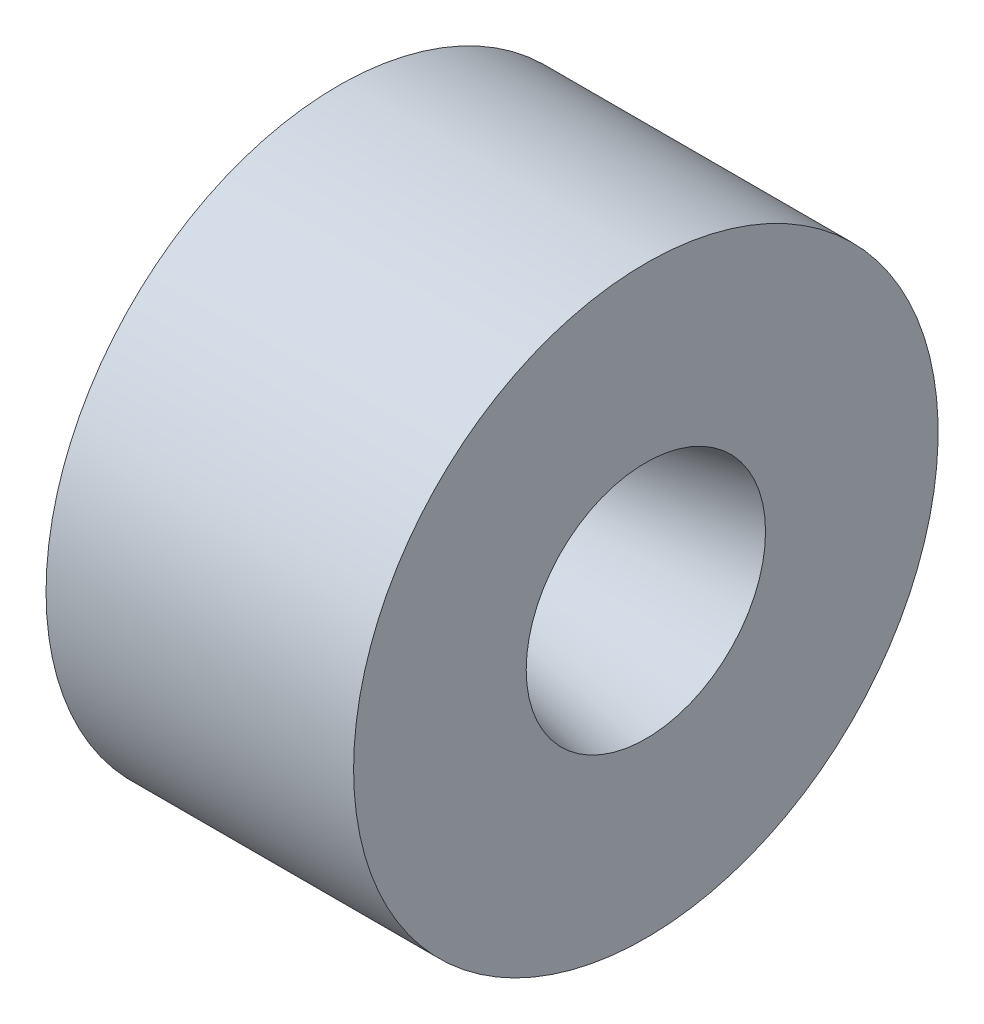
SolidWorks part; units mm, degrees
material "BUTYL"
ref_plane "Front Plane" through (0, 0, 0) normal (0, 0, 1) x (1, 0, 0)
ref_plane "Top Plane" through (0, 0, 0) normal (0, 1, 0) x (1, 0, 0)
ref_plane "Right Plane" through (0, 0, 0) normal (1, 0, 0) x (0, 0, -1)
sketch "Sketch1" plane through (0, 0, 0) normal (0, 0, 1) x (1, 0, 0)
  line L1 (0, -139.7) -> (-73.5, -139.7)
  line L2 (-73.5, -139.7) -> (-73.5, -57.2)
  line L4 (-13.5, -41.25) -> (-13.5, -20)
  line L6 (-62.8571, 0) -> (53.4694, 0) construction
  line L7 (0, -139.7) -> (73.5, -139.7)
  line L8 (73.5, -139.7) -> (73.5, -57.2)
  line L9 (73.5, -57.2) -> (-5.499, -41.25)
  line L10 (-5.499, -41.25) -> (-5.499, -20)
  line L12 (-13.5, -20) -> (-5.499, -20)
  line L13 (-73.5, -57.2) -> (-13.5, -41.25)
  dimension "D1" = 20
  dimension "D2" = 139.7
  dimension "D3" = 41.25
  dimension "D4" = 147
  dimension "D5" = 60
  dimension "D6" = 8.001
  dimension "D7" = 82.5
  dimension "D8" = 82.5
revolve "Revolve1" add sketch "Sketch1" angle 360 about L6
hole_wizard "M8 Clearance Hole1" positions "Sketch5" profile "Sketch4" hole size "M8" standard "ANSI Metric" end condition through all
sketch "Sketch5" plane through (-13.5, 0, 0) normal (-1, 0, 0) x (0, 0, 1)
  circle A0 centre (0, 0) radius 29
  point P5 (0, -29)
  point P12 (-25.1147, 14.5)
  point P13 (25.1147, 14.5)
  dimension "D1" = 58
  dimension "D2" = 3
sketch "Sketch4" plane through (-13.5, 14.5, 25.1147) normal (0, 1, 0) x (0, 0, 1)
  line L0 (0, 0) -> (0, 87)
  line L1 (0, 87) -> (5, 87)
  line L2 (5, 87) -> (5, 0)
  line L5 (5, 0) -> (0, 0)
  line L11 (0, -6.35) -> (0, 107.95) construction
  dimension "Thru Hole Dia." = 10
  dimension "Thru Hole Depth" = 87
